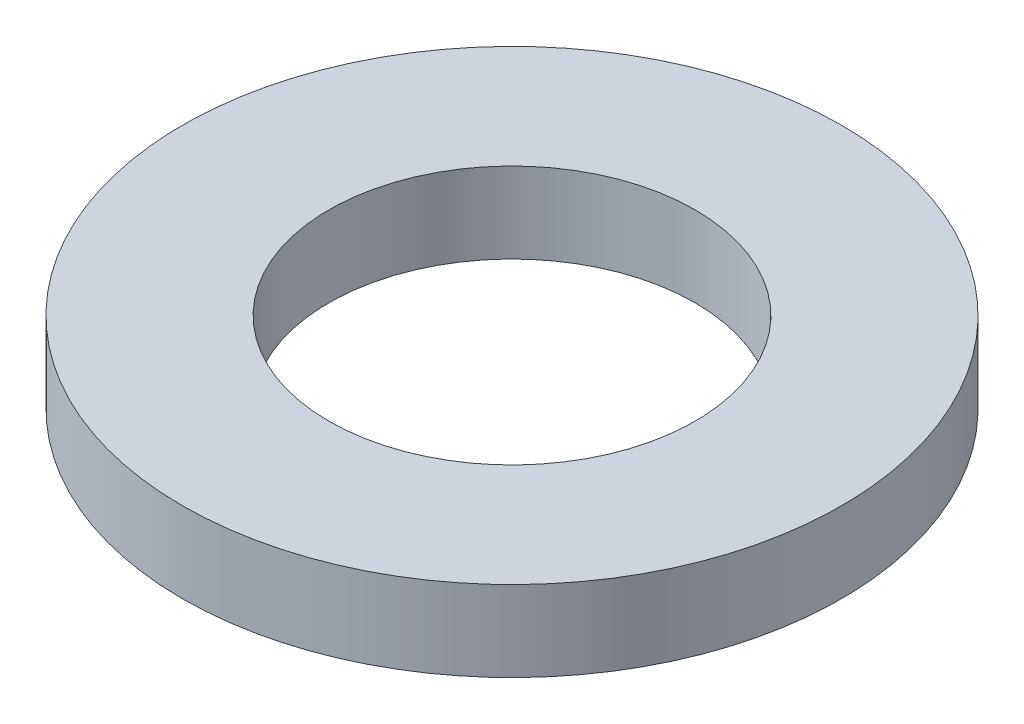
SolidWorks part; units mm, degrees
ref_plane "Front Plane" through (0, 0, 0) normal (0, 0, 1) x (1, 0, 0)
ref_plane "Top Plane" through (0, 0, 0) normal (0, 1, 0) x (1, 0, 0)
ref_plane "Right Plane" through (0, 0, 0) normal (1, 0, 0) x (0, 0, -1)
sketch "Sketch1" plane through (0, 0, 0) normal (0, 1, 0) x (1, 0, 0)
  circle A0 centre (0, 0) radius 90
  dimension "FLANGE_OD" = 180
extrude "Boss-Extrude1" add sketch "Sketch1" along normal blind 22
sketch "Sketch2" plane through (0, 0, 0) normal (0, 1, 0) x (1, 0, 0)
  circle A0 centre (0, 0) radius 50
  dimension "BORE_D" = 100
extrude "Cut-Extrude1" cut sketch "Sketch2" along normal through all
sketch "Sketch3" plane through (0, 22, 0) normal (0, 1, 0) x (1, 0, 0)
  circle A0 centre (0, 0) radius 29.4418 construction
  circle A1 centre (-29.4418, 0) radius 2.9414
  dimension "BOLT_D" = 5.8829
  dimension "BOLT_PCD" = 58.8835
extrude "Cut-Extrude2" cut sketch "Sketch3" against normal blind 19.8893 rebuild error yes
pattern_circular "CirPattern1" count 3 over 360 rebuild error yes
